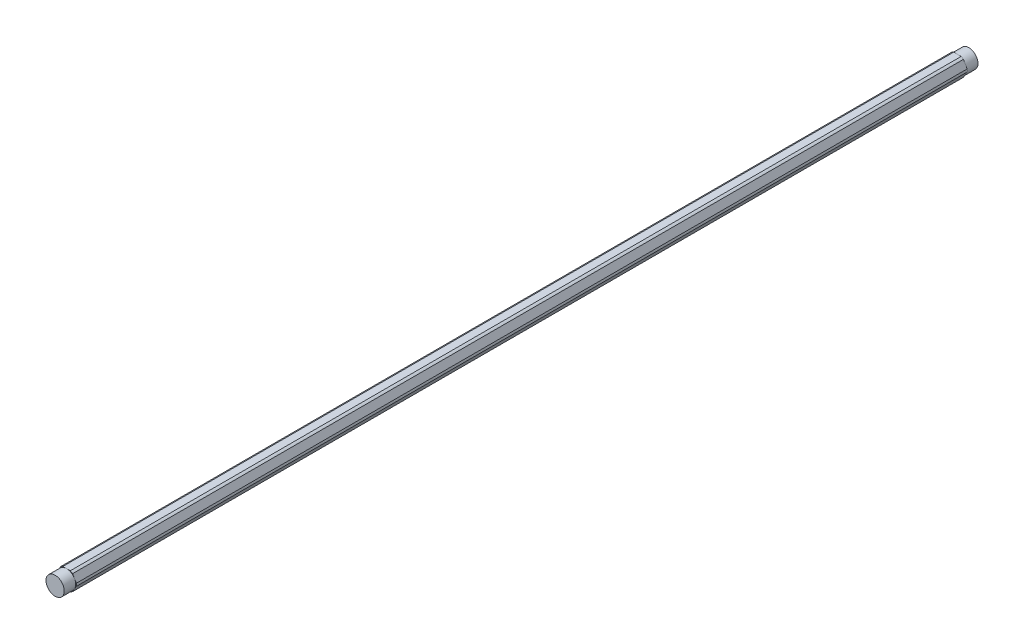
SolidWorks part; units mm, degrees
ref_plane "Front Plane" through (0, 0, 0) normal (0, 0, 1) x (1, 0, 0)
ref_plane "Top Plane" through (0, 0, 0) normal (0, 1, 0) x (1, 0, 0)
ref_plane "Right Plane" through (0, 0, 0) normal (1, 0, 0) x (0, 0, -1)
sketch "Sketch1" plane through (0, 0, 0) normal (0, 0, 1) x (1, 0, 0)
  line L1 (7.3323, 0) -> (3.6662, 6.35)
  line L2 (3.6662, 6.35) -> (-3.6662, 6.35)
  line L3 (-3.6662, 6.35) -> (-7.3323, 0)
  line L4 (-7.3323, 0) -> (-3.6662, -6.35)
  line L5 (-3.6662, -6.35) -> (3.6662, -6.35)
  line L6 (3.6662, -6.35) -> (7.3323, 0)
  circle A0 centre (0, 0) radius 6.35 construction
  dimension "D1" = 12.7
extrude "Boss-Extrude1" add sketch "Sketch1" along normal mid plane 635
sketch "Sketch3" plane through (0, 0, 317.5) normal (0, 0, 1) x (1, 0, 0)
  circle A0 centre (0, 0) radius 6.35
extrude "Cut-Extrude2" cut sketch "Sketch3" against normal blind 7.9502 flip side to cut
mirror "Mirror1" about plane through (0, 0, 0) normal (0, 0, 1) of "Cut-Extrude2"
sketch "Sketch4" plane through (0, 0, 317.5) normal (0, 0, 1) x (1, 0, 0)
  circle A0 centre (0, 0) radius 6.858
  dimension "D1" = 13.716
extrude "Cut-Extrude3" cut sketch "Sketch4" against normal through all flip side to cut
